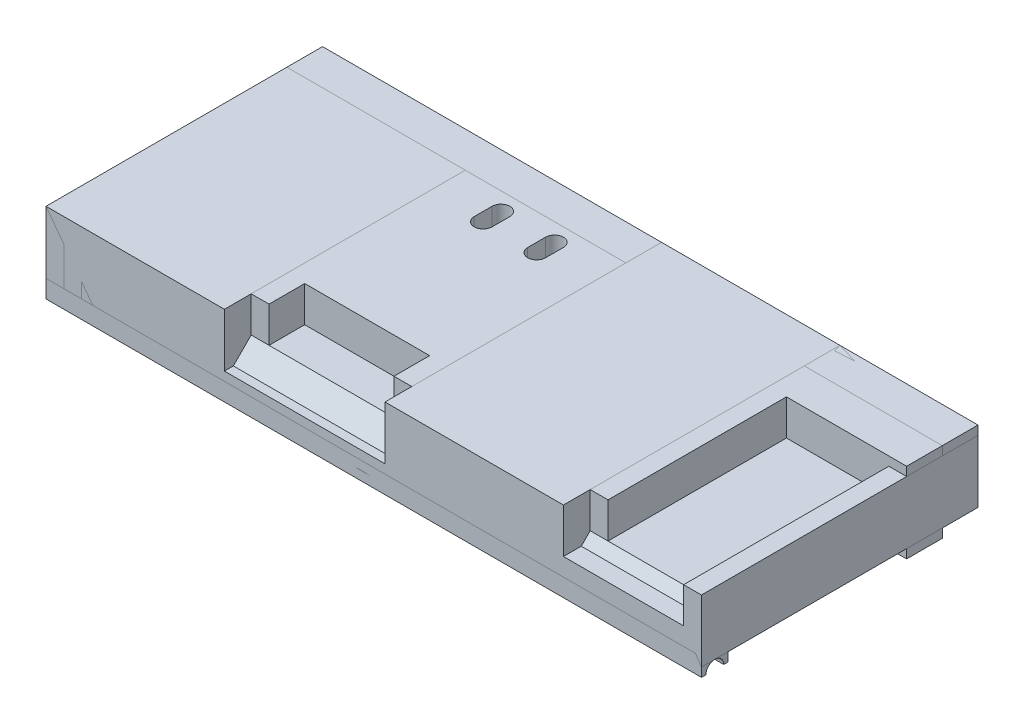
SolidWorks part; units mm, degrees
ref_plane "Front Plane" through (0, 0, 0) normal (0, 0, 1) x (1, 0, 0)
ref_plane "Top Plane" through (0, 0, 0) normal (0, 1, 0) x (1, 0, 0)
ref_plane "Right Plane" through (0, 0, 0) normal (1, 0, 0) x (0, 0, -1)
sketch "Sketch1" plane through (0, 0, 0) normal (0, 1, 0) x (1, 0, 0)
  line L0 (0, -2.3813) -> (0, 22.225)
  line L1 (0, 22.225) -> (46.0375, 22.225)
  line L2 (46.0375, 22.225) -> (56.7309, 19.05)
  line L3 (56.7309, 19.05) -> (58.3184, 19.05)
  line L4 (58.3184, 19.05) -> (58.3184, 15.875)
  line L5 (58.3184, 15.875) -> (47.625, 15.875)
  line L6 (47.625, 15.875) -> (47.625, 0)
  line L7 (47.625, 0) -> (28.575, 0)
  line L8 (28.575, 0) -> (28.575, 3.175)
  line L9 (28.575, 3.175) -> (17.4625, 3.175)
  line L10 (17.4625, 3.175) -> (17.4625, 0)
  line L11 (17.4625, 0) -> (4.7625, 0)
  line L12 (4.7625, 0) -> (4.7625, -2.3813)
  line L13 (4.7625, -2.3813) -> (3.175, -2.3813)
  line L14 (3.175, -2.3813) -> (3.175, 0)
  line L15 (3.175, 0) -> (1.5875, 0)
  line L16 (1.5875, 0) -> (1.5875, -2.3813)
  line L17 (1.5875, -2.3813) -> (0, -2.3813)
  line L18 (25.4, 17.4625) -> (20.6375, 17.4625) construction
  line L19 (19.8437, 17.4625) -> (19.8437, 15.875)
  line L20 (21.4312, 15.875) -> (21.4312, 17.4625)
  line L21 (26.1937, 17.4625) -> (26.1938, 15.875)
  line L22 (24.6062, 15.875) -> (24.6062, 17.4625)
  arc A0 (21.4312, 17.4625) -> (19.8437, 17.4625) centre (20.6375, 17.4625) ccw
  arc A1 (19.8437, 15.875) -> (21.4312, 15.875) centre (20.6375, 15.875) ccw
  arc A2 (24.6062, 17.4625) -> (26.1937, 17.4625) centre (25.4, 17.4625) cw
  arc A3 (26.1938, 15.875) -> (24.6062, 15.875) centre (25.4, 15.875) cw
  point P3 (23.0187, 3.175)
  point P22 (23.0187, 17.4625)
  dimension "D16" = 0.7937
  dimension "D1" = 22.225
  dimension "D2" = 46.0375
  dimension "D3" = 10.6934
  dimension "D4" = 3.175
  dimension "D5" = 1.5875
  dimension "D6" = 3.175
  dimension "D7" = 47.625
  dimension "D8" = 19.05
  dimension "D9" = 3.175
  dimension "D10" = 11.1125
  dimension "D11" = 2.3813
  dimension "D12" = 1.5875
  dimension "D13" = 1.5875
  dimension "D14" = 17.4625
  dimension "D15" = 4.7625
  dimension "D17" = 1.5875
sketch "Sketch2" plane through (0, 0, 0) normal (0, 0, 1) x (1, 0, 0)
  line L0 (0, -0.7938) -> (0, 6.35)
  line L1 (0, 6.35) -> (15.875, 6.35)
  line L2 (15.875, 6.35) -> (15.875, 1.5875)
  line L3 (15.875, 1.5875) -> (30.1625, 1.5875)
  line L4 (30.1625, 1.5875) -> (30.1625, 6.35)
  line L5 (30.1625, 6.35) -> (46.0375, 6.35)
  line L6 (46.0375, 6.35) -> (46.0375, 2.3812)
  line L7 (46.0375, 2.3812) -> (56.7309, 2.3812)
  line L8 (56.7309, 2.3812) -> (56.7309, 5.5562)
  line L9 (56.7309, 5.5562) -> (58.3184, 5.5562)
  line L10 (58.3184, 5.5562) -> (58.3184, 0)
  line L11 (58.3184, 0) -> (4.7625, 0)
  line L12 (4.7625, 0) -> (4.7625, -0.7937)
  line L13 (4.7625, -0.7937) -> (3.175, -0.7937)
  line L14 (3.175, -0.7937) -> (3.175, 0)
  line L15 (3.175, 0) -> (1.5875, 0)
  line L16 (1.5875, 0) -> (1.5875, -0.7938)
  line L17 (1.5875, -0.7938) -> (0, -0.7938)
  dimension "D1" = 6.35
  dimension "D2" = 15.875
  dimension "D3" = 1.5875
  dimension "D4" = 46.0375
  dimension "D5" = 3.9688
  dimension "D6" = 1.5875
  dimension "D7" = 58.3184
  dimension "D8" = 5.5562
  dimension "D9" = 0.7937
  dimension "D10" = 1.5875
  dimension "D11" = 1.5875
sketch "Sketch3" plane through (0, 0, 0) normal (1, 0, 0) x (0, 0, -1)
  line L0 (0, 3.175) -> (20.6375, 3.175)
  line L1 (20.6375, 3.175) -> (20.6375, 4.7625)
  line L2 (20.6375, 4.7625) -> (19.05, 5.3403)
  line L3 (19.05, 5.3403) -> (19.05, 6.35)
  line L4 (19.05, 6.35) -> (22.225, 6.35)
  line L5 (22.225, 6.35) -> (22.225, 0)
  line L6 (22.225, 0) -> (0, 0)
  line L7 (0, 0) -> (0, -0.7937)
  line L8 (0, -0.7937) -> (-0.3969, -0.7938)
  line L9 (-1.9844, -0.7938) -> (-2.3813, -0.7938)
  line L10 (-2.3813, -0.7938) -> (-2.3813, 0.7937)
  line L11 (-2.3813, 0.7937) -> (0, 3.175)
  arc A0 (-0.3969, -0.7938) -> (-1.9844, -0.7938) centre (-1.1906, -0.7938) ccw
  point P14 (-5.7667, -1.268)
  point P16 (-2.8595, -1.2132)
  point P17 (-4.5599, 0.4873)
  point P18 (0, 0)
  point P19 (-0.4005, -1.2003)
  point P20 (-3.7568, -1.1257)
  point P21 (-1.1712, -1.1008)
  point P22 (-2.464, 0.4655)
  dimension "D9" = 0.7937
  dimension "D1" = 3.175
  dimension "D2" = 20.6375
  dimension "D3" = 1.5875
  dimension "D4" = 110
  dimension "D5" = 1.5875
  dimension "D6" = 3.175
  dimension "D7" = 6.35
  dimension "D8" = 0.7937
  dimension "D10" = 2.3813
  dimension "D11" = 0.7937
extrude "Boss-Extrude1" add sketch "Sketch1" along normal blind 6.35 and the other way blind 0.7937
extrude "Boss-Extrude2" add sketch "Sketch2" along normal blind 2.3813 and the other way blind 22.225 separate body
extrude "Boss-Extrude3" add sketch "Sketch3" along normal blind 58.3184 separate body
